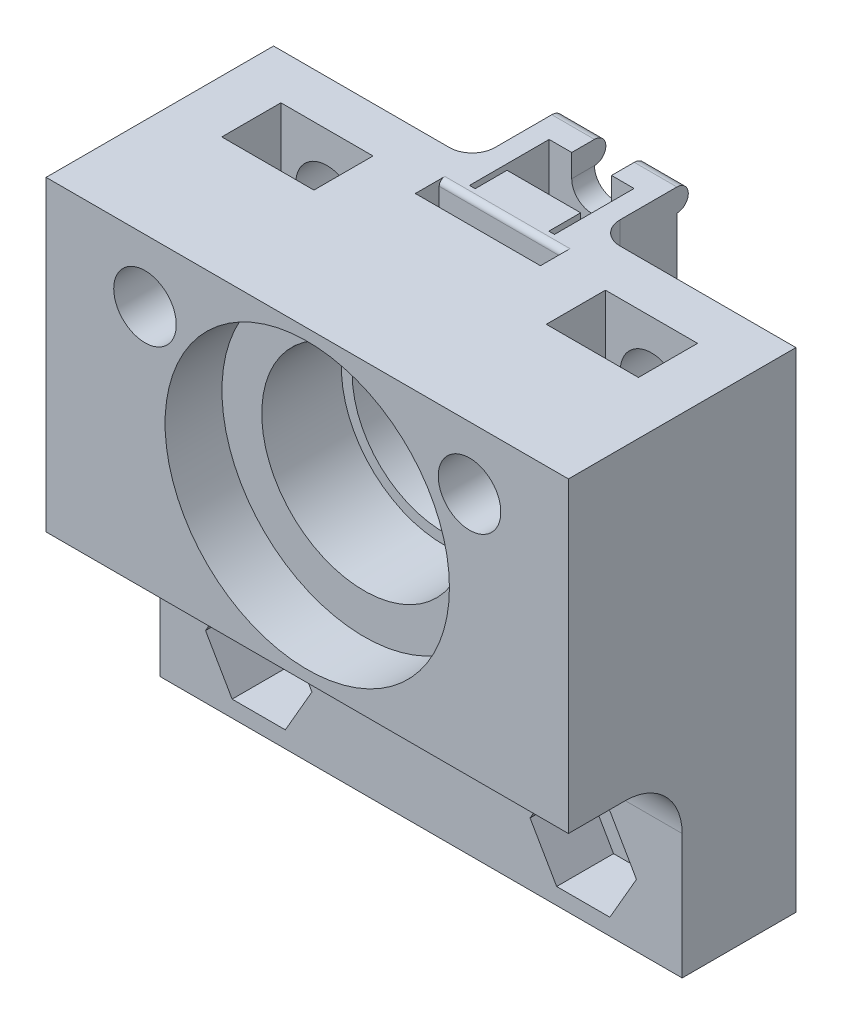
SolidWorks part; units mm, degrees
ref_plane "Front Plane" through (0, 0, 0) normal (0, 0, 1) x (1, 0, 0)
ref_plane "Top Plane" through (0, 0, 0) normal (0, 1, 0) x (1, 0, 0)
ref_plane "Right Plane" through (0, 0, 0) normal (1, 0, 0) x (0, 0, -1)
sketch "Sketch1" plane through (0, 0, 0) normal (0, 1, 0) x (1, 0, 0)
  line L0 (0, 0) -> (-22.961, -55.4328)
  line L1 (0, 0) -> (22.961, -55.4328)
  line L2 (0, 0) -> (0, -29.5283) construction
  circle A0 centre (0, 0) radius 60
  circle A1 centre (0, 0) radius 55
  circle A2 centre (0, 0) radius 50
  circle A3 centre (0, 0) radius 45
  dimension "D1" = 120
  dimension "D2" = 5
  dimension "D3" = 5
  dimension "D4" = 5
  dimension "D5" = 45
extrude "Boss-Extrude1" add sketch "Sketch1" along normal mid plane 27 contours A1 L0 A0 L1 | A2 L0 A1 L1 | A3 L0 A2 L1 region at (0, 0, 46.3313) region at (0, 0, 51.1997) region at (0, 0, 56.0688)
extrude "Boss-Extrude2" add sketch "Sketch1<3>" along normal mid plane 37 contours A2 L0 A1 L1 region at (0, 0, 51.1997)
sketch "Sketch1<3>" plane through (0, 0, 0) normal (0, 1, 0) x (1, 0, 0) same geometry as "Sketch1"
ref_plane "Plane1" through (0, 0, 60) normal (0, 0, 1) x (1, 0, 0)
sketch "Sketch3" plane through (0, 0, 0) normal (0, -1, 0) x (1, 0, 0)
  line L0 (-22.961, 55.4328) -> (-22.961, 266)
  line L1 (-22.961, 266) -> (22.961, 266)
  line L2 (22.961, 266) -> (22.961, 55.4328)
  line L3 (-17.961, 57.2486) -> (-17.961, 246)
  line L4 (-17.961, 246) -> (17.961, 246)
  line L5 (17.961, 246) -> (17.961, 57.2486)
  arc A0 (22.961, 55.4328) -> (-22.961, 55.4328) centre (0, 0) ccw construction
  arc A1 (22.961, 55.4328) -> (-22.961, 55.4328) centre (0, 0) ccw
  dimension "D1" = 5
  dimension "D2" = 5
  dimension "D3" = 20
  dimension "D4" = 266
extrude "Boss-Extrude3" add sketch "Sketch3" against normal mid plane 10 contours L3 A1 L0 L1 L2 L5 L4 region at (-20.8058, 0, 160.7164)
sketch "Sketch4" plane through (0, 0, 0) normal (0, 1, 0) x (1, 0, 0)
  line L0 (22.961, -266) -> (22.961, -55.4328) construction
  line L1 (-22.961, -266) -> (22.961, -266)
  line L2 (-22.961, -266) -> (-22.961, -246)
  line L3 (-22.961, -246) -> (22.961, -246)
  line L4 (22.961, -266) -> (22.961, -246)
  line L5 (-17.961, -246) -> (17.961, -246) construction
extrude "Boss-Extrude4" add sketch "Sketch4" along normal mid plane 27
sketch "Sketch2" plane through (0, 0, 0) normal (0, 0, 1) x (1, 0, 0)
  circle A0 centre (0, 0) radius 4.25
  dimension "D1" = 8.5
extrude "Cut-Extrude1" cut sketch "Sketch2" along normal through all
sketch "Sketch5" plane through (0, 0, 246) normal (0, 0, -1) x (-1, 0, 0)
  circle A0 centre (0, 0) radius 8.05
  dimension "D1" = 16.1
extrude "Cut-Extrude2" [suppressed] cut sketch "Sketch5" against normal blind 4 contours A0
sketch "Sketch6" plane through (0, 0, 266) normal (0, 0, 1) x (1, 0, 0)
  circle A0 centre (0, 0) radius 9
  dimension "D1" = 18
extrude "Cut-Extrude3" cut sketch "Sketch6" against normal blind 12
sketch "Sketch7" plane through (0, 0, 266) normal (0, 0, 1) x (1, 0, 0)
  circle A0 centre (0, 0) radius 12.5
  dimension "D1" = 25
extrude "Cut-Extrude4" cut sketch "Sketch7" against normal blind 5
sketch "Sketch9" plane through (0, 0, 0) normal (0, 1, 0) x (1, 0, 0)
  line L0 (-22.961, -55.4328) -> (-22.961, -68)
  line L1 (-22.961, -55.4328) -> (-22.961, -246) construction
  line L2 (-22.961, -68) -> (22.961, -68)
  line L3 (22.961, -246) -> (22.961, -55.4328) construction
  line L4 (22.961, -68) -> (22.961, -55.4328)
  arc A0 (-22.961, -55.4328) -> (22.961, -55.4328) centre (0, 0) ccw construction
  arc A1 (-22.961, -55.4328) -> (22.961, -55.4328) centre (0, 0) ccw
  point P3 (0, -60)
  dimension "D1" = 8
extrude "Boss-Extrude5" add sketch "Sketch9" along normal mid plane 27
sketch "Sketch8" plane through (0, 0, 60) normal (0, 0, 1) x (1, 0, 0)
  circle A0 centre (0, 0) radius 9
  dimension "D1" = 18
extrude "Cut-Extrude5" cut sketch "Sketch8" against normal up to next
sketch "Sketch10" plane through (0, 0, 60) normal (0, 0, 1) x (1, 0, 0)
  circle A0 centre (0, 0) radius 4
  dimension "D1" = 8
extrude "Cut-Extrude6" cut sketch "Sketch10" along normal up to next
sketch "Sketch11" plane through (0, 0, 68) normal (0, 0, 1) x (1, 0, 0)
  circle A0 centre (0, 0) radius 8
  dimension "D1" = 16
extrude "Cut-Extrude7" cut sketch "Sketch11" against normal blind 4
sketch "Sketch18" plane through (0, 0, 0) normal (0, 0, 1) x (1, 0, 0)
  circle A0 centre (0, 0) radius 11
  dimension "D1" = 22
extrude "Cut-Extrude9" cut sketch "Sketch18" along normal blind 47
sketch "Sketch19" plane through (0, 0, 0) normal (0, 1, 0) x (1, 0, 0)
  line L1 (-22.961, -68) -> (22.961, -68)
  line L2 (-22.961, -68) -> (-22.961, -266)
  line L3 (-22.961, -266) -> (22.961, -266)
  line L4 (22.961, -68) -> (22.961, -266)
sketch "Sketch20" plane through (0, 0, 0) normal (0, 1, 0) x (1, 0, 0)
  line L0 (22.961, -68) -> (22.961, -266) construction
  line L1 (-22.961, -246) -> (22.961, -246)
  line L2 (-22.961, -246) -> (-22.961, -41.5746)
  line L3 (-22.961, -41.5746) -> (22.961, -41.5746)
  line L4 (22.961, -246) -> (22.961, -41.5746)
extrude "Cut-Extrude11" cut sketch "Sketch20" against normal through all both and the other way through all
sketch "Sketch21" plane through (0, -13.5, 0) normal (0, -1, 0) x (1, 0, 0)
  line L0 (22.961, 266) -> (22.961, 246) construction
  line L1 (-22.961, 246) -> (22.961, 246)
  line L2 (-22.961, 246) -> (-22.961, 256)
  line L3 (-22.961, 256) -> (22.961, 256)
  line L4 (22.961, 246) -> (22.961, 256)
extrude "Boss-Extrude6" add sketch "Sketch21" along normal blind 16
hole_wizard "M5 Clearance Hole1" positions "Sketch22" profile "Sketch23" hole size "M5" standard "ISO" end condition through all
sketch "Sketch22" plane through (0, 0, 246) normal (0, 0, -1) x (-1, 0, 0)
  line L0 (22.961, -29.5) -> (-22.961, -29.5) construction
  line L1 (-22.961, 13.5) -> (-22.961, -29.5) construction
  point P2 (-14.2661, -24)
  dimension "D1" = 5.5
  dimension "D2" = 8.6949
sketch "Sketch23" plane through (14.2661, -24, 246) normal (1, 0, 0) x (0, 1, 0)
  line L0 (0, 0) -> (0, 20)
  line L1 (0, 20) -> (2.75, 20)
  line L2 (2.75, 20) -> (2.75, 0)
  line L5 (2.75, 0) -> (0, 0)
  line L11 (0, -6.35) -> (0, 107.95) construction
  dimension "Thru Hole Dia." = 5.5
  dimension "Thru Hole Depth" = 20
sketch "Sketch24" plane through (0, 0, 256) normal (0, 0, 1) x (1, 0, 0)
  line L1 (18.9426, -24) -> (16.6043, -19.95)
  line L2 (16.6043, -19.95) -> (11.9278, -19.95)
  line L3 (11.9278, -19.95) -> (9.5895, -24)
  line L4 (9.5895, -24) -> (11.9278, -28.05)
  line L5 (11.9278, -28.05) -> (16.6043, -28.05)
  line L6 (16.6043, -28.05) -> (18.9426, -24)
  circle A0 centre (14.2661, -24) radius 4.05 construction
  dimension "D1" = 8.1
extrude "Cut-Extrude12" cut sketch "Sketch24" against normal blind 5
mirror "Mirror1" about plane through (0, 0, 0) normal (1, 0, 0) of "M5 Clearance Hole1"
mirror "Mirror2" about plane through (0, 0, 0) normal (1, 0, 0) of "Cut-Extrude12"
fillet "Fillet1" radius 5 1 edges at (0, -13.5, 256)
pattern_linear "LPattern2" count 2 spacing 32 along (0, 1, 0) of "Mirror1"
sketch "Sketch25" plane through (0, 0, 246) normal (0, 0, -1) x (-1, 0, 0)
  line L0 (-18.3161, 10.3383) -> (-18.3161, 13.5)
  line L1 (-18.3161, 10.3383) -> (-18.3161, 5.6617)
  line L2 (-18.3161, 5.6617) -> (-14.2661, 3.3235)
  line L3 (-14.2661, 3.3235) -> (-10.2161, 5.6617)
  line L4 (-10.2161, 5.6617) -> (-10.2161, 10.3383)
  line L5 (-10.2161, 10.3383) -> (-14.2661, 12.6765)
  line L6 (-14.2661, 12.6765) -> (-18.3161, 10.3383)
  line L7 (-22.961, 13.5) -> (22.961, 13.5) construction
  line L8 (-18.3161, 13.5) -> (-10.2161, 13.5)
  line L9 (-10.2161, 13.5) -> (-10.2161, 10.3383)
  circle A0 centre (-14.2661, 8) radius 4.05 construction
  circle M7 centre (-14.2661, 8) radius 2.75
  line M11 (22.961, 13.5) -> (-22.961, 13.5)
  dimension "D1" = 8.1
extrude "Cut-Extrude13" cut sketch "Sketch25" against normal blind 5.2 from offset 4 contours L9 L0 L6 L5 M11 | L5 L6 L1 L2 L3 L4 M7 region at (16.2292, 11.4002, 246) region at (18.2291, 11.9191, 246) offset against normal yes
mirror "Mirror3" about plane through (0, 0, 0) normal (1, 0, 0) of "Cut-Extrude13"
sketch "Sketch26" plane through (0, 0, 254) normal (0, 0, 1) x (1, 0, 0)
  circle A0 centre (0, 0) radius 8.05
  dimension "D1" = 16.1
extrude "Cut-Extrude14" cut sketch "Sketch26" against normal blind 4
sketch "Sketch27" plane through (0, 0, 246) normal (0, 0, -1) x (-1, 0, 0)
  line L0 (-22.961, 13.5) -> (22.961, 13.5) construction
  line L1 (-5.5, 13.5) -> (5.5, 13.5)
  line L2 (-5.5, 13.5) -> (-5.5, 6.5)
  line L3 (-5.5, 6.5) -> (5.5, 6.5)
  line L4 (5.5, 13.5) -> (5.5, 6.5)
  point P6 (0, 13.5)
  dimension "D1" = 11
  dimension "D2" = 7
extrude "Boss-Extrude7" add sketch "Sketch27" along normal blind 5
sketch "Sketch28" plane through (0, 13.5, 0) normal (0, 1, 0) x (1, 0, 0)
  line L0 (-3.735, -241) -> (3.735, -241)
  line L1 (-5.5, -241) -> (5.5, -241) construction
  line L2 (3.735, -241) -> (3.735, -248)
  line L3 (3.735, -248) -> (3.235, -248)
  line L4 (3.235, -248) -> (3.235, -245.2)
  line L5 (3.235, -245.2) -> (-3.235, -245.2)
  line L6 (-3.235, -245.2) -> (-3.235, -248)
  line L7 (-3.235, -248) -> (-3.735, -248)
  line L8 (-3.735, -248) -> (-3.735, -241)
  point P8 (0, -241)
  dimension "D1" = 7.47
  dimension "D2" = 0.5
  dimension "D3" = 4.2
  dimension "D4" = 7
extrude "Cut-Extrude15" cut sketch "Sketch28" against normal blind 5
fillet "Fillet2" radius 2 3 edges at (0, 6.5, 246) (5.5, 10, 246) (-5.5, 10, 246)
sketch "Sketch29" plane through (0, 0, 241) normal (0, 0, -1) x (-1, 0, 0)
  line L0 (-1.75, 11.5) -> (-1.75, 13.5)
  line L1 (-5.5, 13.5) -> (5.5, 13.5)
  line L2 (-5.5, 13.5) -> (-5.5, 6.5)
  line L3 (-5.5, 6.5) -> (5.5, 6.5)
  line L4 (5.5, 13.5) -> (5.5, 6.5)
  line L5 (1.75, 11.5) -> (1.75, 13.5)
  circle A0 centre (0, 11.5) radius 1.75
  line M6 (3.735, 13.5) -> (3.735, 8.5)
  line M7 (3.735, 8.5) -> (-3.735, 8.5)
  line M8 (-3.735, 8.5) -> (-3.735, 13.5)
  line M9 (-3.735, 13.5) -> (-5.5, 13.5)
  line M10 (-5.5, 13.5) -> (-5.5, 6.5)
  line M11 (-5.5, 6.5) -> (5.5, 6.5)
  line M12 (5.5, 6.5) -> (5.5, 13.5)
  line M13 (5.5, 13.5) -> (3.735, 13.5)
  dimension "D1" = 3.5
  dimension "D2" = 5
extrude "Boss-Extrude8" add sketch "Sketch29" along normal blind 2 contours M13 M6 M7 M8 M9 M10 M11 M12 | A0 L0 L1 L5 M8 M7 M6 region at (0, 9.6601, 241) region at (3.8654, 11, 241)
sketch "Sketch30" plane through (-5.5, 0, 0) normal (-1, 0, 0) x (0, 0, 1)
  line L0 (239, 6.5) -> (239, 13.5) construction
  line L1 (239, 11.5) -> (239, 13.5)
  arc A0 (239, 13.5) -> (239, 11.5) centre (239, 12.5) ccw
  dimension "D1" = 1
extrude "Boss-Extrude9" add sketch "Sketch30" against normal blind 3.75
mirror "Mirror4" about plane through (0, 0, 0) normal (1, 0, 0) of "Boss-Extrude9"
sketch "Sketch31" plane through (0, 13.5, 0) normal (0, 1, 0) x (1, 0, 0)
  line L0 (22.961, -246) -> (7.5, -246) construction
  line L1 (5.5, -248.9) -> (-5.5, -248.9)
  line L2 (5.5, -248.9) -> (5.5, -251)
  line L3 (5.5, -251) -> (-5.5, -251)
  line L4 (-5.5, -248.9) -> (-5.5, -251)
  line L5 (-3.235, -245.2) -> (3.235, -245.2) construction
  point P6 (0, -248.9)
  point P9 (0, -245.2)
  dimension "D1" = 5
  dimension "D2" = 2.1
  dimension "D3" = 11
extrude "Cut-Extrude16" cut sketch "Sketch31" against normal blind 2.5
fillet "Fillet3" radius 0.5 1 edges at (0, 13.5, 248.9)
sketch "Sketch32" plane through (0, 0, 246) normal (0, 0, -1) x (-1, 0, 0)
  circle A0 centre (0, 0) radius 4.5
  dimension "D1" = 9
extrude "Cut-Extrude17" cut sketch "Sketch32" against normal up to next
